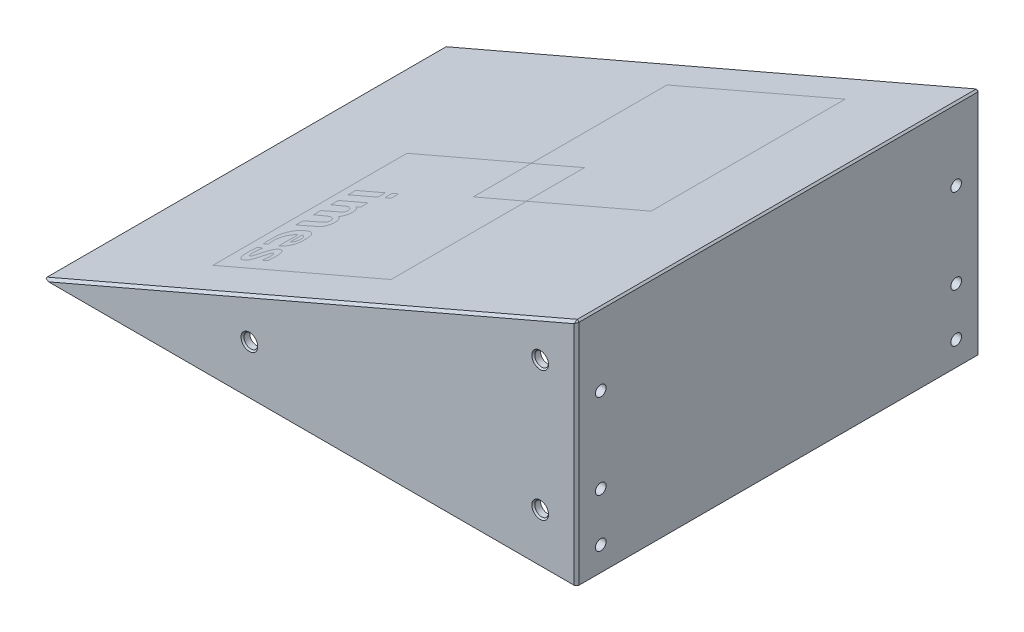
SolidWorks part; units mm, degrees
note: The reader was unsure of these and kept them because the rebuilt part matched: shared geometry of "Sketch13<3>", "Sketch13<4>".
ref_plane "Front Plane" through (0, 0, 0) normal (0, 0, 1) x (1, 0, 0)
ref_plane "Top Plane" through (0, 0, 0) normal (0, 1, 0) x (1, 0, 0)
ref_plane "Right Plane" through (0, 0, 0) normal (1, 0, 0) x (0, 0, -1)
sketch "Sketch1" plane through (0, 0, 0) normal (0, 0, 1) x (1, 0, 0)
  line L0 (0, 0) -> (-220.3974, 0)
  line L1 (-220.3974, 0) -> (0, 95)
  line L2 (0, 95) -> (0, 0)
  dimension "D1" = 240
extrude "Boss-Extrude1" add sketch "Sketch1" along normal blind 166.6667
ref_plane "Plane1" through (0, 0, 163.6667) normal (0, 0, 1) x (1, 0, 0)
sketch "Sketch2" plane through (0, 0, 163.6667) normal (0, 0, 1) x (1, 0, 0)
  line L0 (-5, 0) -> (-5, 87.4001)
  line L1 (-220.3974, 0) -> (0, 0) construction
  line L2 (-5, 87.4001) -> (-178.2213, 12.7348)
  line L3 (-178.2213, 12.7348) -> (-178.2213, 0)
  line L4 (-178.2213, 0) -> (-5, 0)
  line L5 (0, 95) -> (-220.3974, 0) construction
  line L6 (0, 0) -> (0, 95) construction
  dimension "D1" = 188.628
  dimension "D2" = 5
  dimension "D3" = 5
extrude "Cut-Extrude1" cut sketch "Sketch2" against normal offset from surface (160.6667 mm away) 3 up to face at (-73.4658, 31.6667, 0)
sketch "Sketch3" plane through (0, 0, 0) normal (1, 0, 0) x (0, 0, -1)
  line L0 (-156.6667, 0) -> (-156.6667, 95) construction
  line L1 (-166.6667, 0) -> (0, 0) construction
  line L2 (-166.6667, 95) -> (0, 95) construction
  line L3 (-166.6667, 0) -> (-166.6667, 95) construction
  line L4 (-83.3333, 95) -> (-83.3333, 0) construction
  line L5 (-10, 0) -> (-10, 95) construction
  circle A0 centre (-156.6667, 10) radius 2.2
  circle A1 centre (-156.6667, 65) radius 2.2
  circle A2 centre (-156.6667, 30) radius 2.2
  circle A3 centre (-10, 30) radius 2.2
  circle A4 centre (-10, 65) radius 2.2
  circle A5 centre (-10, 10) radius 2.2
  dimension "D2" = 4.4
  dimension "D3" = 10
  dimension "D4" = 20
  dimension "D5" = 30
  dimension "D1" = 10
extrude "Cut-Extrude2" cut sketch "Sketch3" against normal up to surface (5 mm away) up to face at (-5, 43.7, 83.3333)
sketch "Sketch4" plane through (0, 0, 0) normal (0, 0, -1) x (-1, 0, 0)
  line L0 (15, 0) -> (15, 88.5344) construction
  line L1 (220.3974, 0) -> (0, 0) construction
  line L2 (0, 95) -> (220.3974, 0) construction
  line L3 (0, 0) -> (0, 95) construction
  line L4 (15, 20) -> (135, 20) construction
  circle A0 centre (15, 73.5344) radius 2.2
  circle A1 centre (15, 20) radius 2.2
  circle A2 centre (135, 20) radius 2.2
  dimension "D1" = 4.4
  dimension "D2" = 20
  dimension "D3" = 15
  dimension "D4" = 15
  dimension "D5" = 120
extrude "Cut-Extrude3" cut sketch "Sketch4" against normal up to surface (163.6667 mm away)
ref_plane "Plane2" through (0, 0, 83.3333) normal (0, 0, -1) x (-1, 0, 0)
mirror "Mirror1" about plane through (0, 0, 83.3333) normal (0, 0, -1) of "Cut-Extrude3"
chamfer "Chamfer1" distance 1 angle 45 6 edges at (-220.3974, 0, 83.3333) (0, 95, 83.3333) (0, 47.5, 166.6667) (-110.1987, 47.5, 166.6667) (0, 47.5, 0) (-110.1987, 47.5, 0)
sketch "Sketch13" plane through (-166.8801, 23.068, 13.9635) normal (-0.3958, 0.9183, 0) x (0, 0, 1)
  line L0 (55.9477, 28.1093) -> (55.9477, 56.0832)
  line L1 (55.9477, 56.0832) -> (27.9739, 56.0832)
  line L2 (27.9739, 56.0832) -> (0, 56.0832)
  line L3 (0, 56.0832) -> (0, 96.1136)
  line L4 (0, 96.1136) -> (0, 136.144)
  line L5 (0, 136.144) -> (40.0304, 136.144)
  line L6 (40.0304, 136.144) -> (80.0608, 136.144)
  line L7 (80.0608, 136.144) -> (80.0608, 108.1701)
  line L8 (80.0608, 108.1701) -> (80.0608, 80.1962)
  line L9 (80.0608, 80.1962) -> (108.0347, 80.1962)
  line L10 (108.0347, 80.1962) -> (136.0085, 80.1962)
  line L11 (136.0085, 80.1962) -> (136.0085, 40.1658)
  line L12 (136.0085, 40.1658) -> (136.0085, 0.1354)
  line L13 (136.0085, 0.1354) -> (95.9781, 0.1354)
  line L14 (95.9781, 0.1354) -> (55.9477, 0.1354)
  line L15 (55.9477, 0.1354) -> (55.9477, 28.1093)
  line L16 (119.38, 5.285) -> (120.0235, 5.4406)
  line L17 (120.0235, 5.4406) -> (120.0235, 6.5278)
  line L18 (116.4971, 12.8693) -> (120.4299, 12.8693)
  line L19 (120.4299, 12.8693) -> (120.4288, 13.445)
  line L20 (119.3798, 5.285) -> (119.38, 5.285)
  line L21 (117.4134, 15.1659) -> (117.4853, 14.6304)
  line L22 (117.4853, 14.6304) -> (115.029, 14.6304)
  line L23 (130.3189, 17.2595) -> (130.3189, 18.5339)
  line L24 (130.3189, 18.5339) -> (129.0181, 18.7681)
  line L25 (84.9376, 11.9888) -> (84.9376, 18.6944)
  line L26 (84.9376, 18.6944) -> (83.3797, 18.6944)
  line L27 (83.3797, 18.6944) -> (81.8219, 18.6944)
  line L28 (81.8219, 18.6944) -> (81.8219, 11.9888)
  line L29 (81.8219, 11.9888) -> (81.8219, 5.2832)
  line L30 (81.8219, 5.2832) -> (83.3797, 5.2832)
  line L31 (83.3797, 5.2832) -> (84.9376, 5.2832)
  line L32 (84.9376, 5.2832) -> (84.9376, 11.9888)
  line L33 (95.7918, 15.6286) -> (96.1136, 15.2862)
  line L34 (96.1136, 15.2862) -> (96.1522, 10.2847)
  line L35 (96.1522, 10.2847) -> (96.1909, 5.2832)
  line L36 (96.1909, 5.2832) -> (97.744, 5.2832)
  line L37 (97.744, 5.2832) -> (99.2971, 5.2832)
  line L38 (99.2971, 5.2832) -> (99.2996, 8.5682)
  line L39 (103.4721, 10.1261) -> (103.5151, 5.2832)
  line L40 (103.5151, 5.2832) -> (105.0018, 5.2832)
  line L41 (105.0018, 5.2832) -> (106.4885, 5.2832)
  line L42 (106.4885, 5.2832) -> (106.4489, 10.7357)
  line L43 (99.574, 17.0612) -> (99.077, 16.2924)
  line L44 (99.077, 16.2924) -> (98.8423, 16.9531)
  line L45 (92.5097, 17.2277) -> (92.1175, 16.6093)
  line L46 (92.1175, 16.6093) -> (92.1175, 17.6519)
  line L47 (92.1175, 17.6519) -> (92.1175, 18.6944)
  line L48 (92.1175, 18.6944) -> (90.5597, 18.6944)
  line L49 (90.5597, 18.6944) -> (89.0018, 18.6944)
  line L50 (89.0018, 18.6944) -> (89.0018, 11.9888)
  line L51 (89.0018, 11.9888) -> (89.0018, 5.2832)
  line L52 (89.0018, 5.2832) -> (90.5503, 5.2832)
  line L53 (90.5503, 5.2832) -> (92.0987, 5.2832)
  line L54 (92.0987, 5.2832) -> (92.1453, 9.1101)
  line L55 (84.9376, 23.1648) -> (84.9376, 24.6549)
  line L56 (84.9376, 24.6549) -> (83.3797, 24.6549)
  line L57 (83.3797, 24.6549) -> (81.8219, 24.6549)
  line L58 (81.8219, 24.6549) -> (81.8219, 23.1648)
  line L59 (81.8219, 23.1648) -> (81.8219, 21.6746)
  line L60 (81.8219, 21.6746) -> (83.3797, 21.6746)
  line L61 (83.3797, 21.6746) -> (84.9376, 21.6746)
  line L62 (84.9376, 21.6746) -> (84.9376, 23.1648)
  line L63 (80.0277, 68.1058) -> (80.0623, 80.0608)
  line L64 (80.0623, 80.0608) -> (68.0727, 80.0608)
  line L65 (68.0727, 80.0608) -> (56.0832, 80.0608)
  line L66 (56.0832, 80.0608) -> (56.0832, 68.0712)
  line L67 (56.0832, 68.0712) -> (56.0832, 56.0817)
  line L68 (56.0832, 56.0817) -> (68.0381, 56.1163)
  line L69 (68.0381, 56.1163) -> (79.9931, 56.1509)
  line L70 (79.9931, 56.1509) -> (80.0277, 68.1058)
  line L71 (56.0832, 56.0817) -> (55.9477, 56.0832)
  line L72 (80.0623, 80.0608) -> (80.0608, 80.2508)
  spline S0 degree 3 poles (120.0235, 6.5278) (120.0235, 7.4768) (119.9954, 7.6043) (119.8028, 7.5304) knots 0 0 0 0 1 1 1 1
  spline S1 degree 3 poles (119.8028, 7.5304) (119.096, 7.2592) (118.2565, 7.1534) (117.2109, 7.2036) knots 0 0 0 0 1 1 1 1
  spline S2 degree 3 poles (117.2109, 7.2036) (116.2244, 7.2511) (115.9063, 7.3264) (115.3017, 7.6558) knots 0 0 0 0 1 1 1 1
  spline S3 degree 3 poles (115.3017, 7.6558) (113.9807, 8.3756) (112.9036, 9.9548) (112.5572, 11.6798) knots 0 0 0 0 1 1 1 1
  spline S4 degree 3 poles (112.5572, 11.6798) (112.3015, 12.9531) (112.024, 12.8693) (116.4971, 12.8693) knots 0 0 0 0 1 1 1 1
  spline S5 degree 3 poles (120.4288, 13.445) (120.4268, 15.0769) (119.8192, 16.8204) (118.9624, 17.6545) knots 0 0 0 0 1 1 1 1
  spline S6 degree 3 poles (118.9624, 17.6545) (118.689, 17.9206) (118.0996, 18.3072) (117.6526, 18.5136) knots 0 0 0 0 1 1 1 1
  spline S7 degree 3 poles (117.6526, 18.5136) (116.9232, 18.8503) (116.6868, 18.8893) (115.3496, 18.8932) knots 0 0 0 0 1 1 1 1
  spline S8 degree 3 poles (115.3496, 18.8932) (113.601, 18.8983) (112.619, 18.6494) (111.7388, 17.9781) knots 0 0 0 0 1 1 1 1
  spline S9 degree 3 poles (111.7388, 17.9781) (110.8801, 17.3232) (110.3098, 16.4939) (109.966, 15.4003) knots 0 0 0 0 1 1 1 1
  spline S10 degree 3 poles (109.966, 15.4003) (109.5683, 14.1354) (109.537, 11.2699) (109.9059, 9.889) knots 0 0 0 0 1 1 1 1
  spline S11 degree 3 poles (109.9059, 9.889) (110.5643, 7.4241) (112.0357, 5.8283) (114.2123, 5.2184) knots 0 0 0 0 1 1 1 1
  spline S12 degree 3 poles (114.2123, 5.2184) (115.0598, 4.9809) (118.2945, 5.0226) (119.3798, 5.285) knots 0 0 0 0 1 1 1 1
  spline S13 degree 3 poles (112.5728, 14.8379) (112.5728, 15.2621) (112.9536, 15.9345) (113.4314, 16.354) knots 0 0 0 0 1 1 1 1
  spline S14 degree 3 poles (113.4314, 16.354) (114.8968, 17.6406) (117.1726, 16.9616) (117.4134, 15.1659) knots 0 0 0 0 1 1 1 1
  spline S15 degree 3 poles (115.029, 14.6304) (112.9131, 14.6304) (112.5728, 14.6591) (112.5728, 14.8379) knots 0 0 0 0 1 1 1 1
  spline S16 degree 3 poles (128.0837, 5.1959) (130.1184, 5.7381) (131.1308, 6.9611) (131.1274, 8.873) knots 0 0 0 0 1 1 1 1
  spline S17 degree 3 poles (131.1274, 8.873) (131.1244, 10.659) (130.5305, 11.4345) (127.802, 13.2159) knots 0 0 0 0 1 1 1 1
  spline S18 degree 3 poles (127.802, 13.2159) (125.8156, 14.5128) (125.3067, 14.9859) (125.3067, 15.5356) knots 0 0 0 0 1 1 1 1
  spline S19 degree 3 poles (125.3067, 15.5356) (125.3067, 16.2783) (126.7192, 16.9245) (127.9105, 16.7268) knots 0 0 0 0 1 1 1 1
  spline S20 degree 3 poles (127.9105, 16.7268) (128.2293, 16.6739) (128.8784, 16.4854) (129.3529, 16.3078) knots 0 0 0 0 1 1 1 1
  spline S21 degree 3 poles (129.3529, 16.3078) (129.8275, 16.1303) (130.2389, 15.985) (130.2673, 15.985) knots 0 0 0 0 1 1 1 1
  spline S22 degree 3 poles (130.2673, 15.985) (130.2957, 15.985) (130.3189, 16.5585) (130.3189, 17.2595) knots 0 0 0 0 1 1 1 1
  spline S23 degree 3 poles (129.0181, 18.7681) (125.2165, 19.4526) (122.5963, 17.9842) (122.6016, 15.1722) knots 0 0 0 0 1 1 1 1
  spline S24 degree 3 poles (122.6016, 15.1722) (122.6047, 13.5145) (123.3273, 12.5517) (125.8526, 10.8401) knots 0 0 0 0 1 1 1 1
  spline S25 degree 3 poles (125.8526, 10.8401) (127.7723, 9.539) (128.2869, 9.0543) (128.2869, 8.5476) knots 0 0 0 0 1 1 1 1
  spline S26 degree 3 poles (128.2869, 8.5476) (128.2869, 7.2086) (125.4698, 6.9556) (122.8344, 8.0578) knots 0 0 0 0 1 1 1 1
  spline S27 degree 3 poles (122.8344, 8.0578) (122.6177, 8.1484) (122.5973, 8.0392) (122.5973, 6.7878) knots 0 0 0 0 1 1 1 1
  spline S28 degree 3 poles (122.5973, 6.7878) (122.5973, 5.7874) (122.6429, 5.4163) (122.7667, 5.4099) knots 0 0 0 0 1 1 1 1
  spline S29 degree 3 poles (122.7667, 5.4099) (122.8598, 5.4053) (123.3017, 5.3188) (123.7488, 5.2181) knots 0 0 0 0 1 1 1 1
  spline S30 degree 3 poles (123.7488, 5.2181) (124.8105, 4.9789) (127.2228, 4.9665) (128.0837, 5.1959) knots 0 0 0 0 1 1 1 1
  spline S31 degree 3 poles (92.1453, 9.1101) (92.1899, 12.7599) (92.207, 12.9747) (92.5133, 13.7498) knots 0 0 0 0 1 1 1 1
  spline S32 degree 3 poles (92.5133, 13.7498) (92.999, 14.9787) (93.5089, 15.6452) (94.1635, 15.9072) knots 0 0 0 0 1 1 1 1
  spline S33 degree 3 poles (94.1635, 15.9072) (94.8473, 16.1808) (95.3543, 16.0941) (95.7918, 15.6286) knots 0 0 0 0 1 1 1 1
  spline S34 degree 3 poles (99.2996, 8.5682) (99.3022, 12.0563) (99.4174, 13.0342) (99.9806, 14.3433) knots 0 0 0 0 1 1 1 1
  spline S35 degree 3 poles (99.9806, 14.3433) (100.5254, 15.6097) (101.6839, 16.3432) (102.5638, 15.9787) knots 0 0 0 0 1 1 1 1
  spline S36 degree 3 poles (102.5638, 15.9787) (103.3998, 15.6324) (103.4245, 15.4734) (103.4721, 10.1261) knots 0 0 0 0 1 1 1 1
  spline S37 degree 3 poles (106.4489, 10.7357) (106.4099, 16.0999) (106.4042, 16.1992) (106.0972, 16.8656) knots 0 0 0 0 1 1 1 1
  spline S38 degree 3 poles (106.0972, 16.8656) (105.5361, 18.0835) (104.6197, 18.7738) (103.367, 18.9222) knots 0 0 0 0 1 1 1 1
  spline S39 degree 3 poles (103.367, 18.9222) (101.906, 19.0952) (100.4161, 18.3642) (99.574, 17.0612) knots 0 0 0 0 1 1 1 1
  spline S40 degree 3 poles (98.8423, 16.9531) (98.5273, 17.84) (97.8459, 18.4967) (96.9708, 18.7566) knots 0 0 0 0 1 1 1 1
  spline S41 degree 3 poles (96.9708, 18.7566) (95.1569, 19.2952) (93.4499, 18.7102) (92.5097, 17.2277) knots 0 0 0 0 1 1 1 1
extrude "Cut-Extrude7" cut sketch "Sketch13" against normal blind 1 contours L15 L14 L13 L12 L11 L10 L9 L8 L7 L6 L5 L4 L3 L2 L1 L0 S41 S40 L44 L43 S39 S38 S37 L42 L41 L40 L39 S36 S35 S34 L38 L37 L36 L35 L34 L33 S33 S32 S31 L54 L53 L52 L51 L50 L49 L48 L47 L46 L45 | S15 L22 L21 S14 S13 | L64 L72 L9 L8 L7 L6 L5 L4 L3 L2 L1 L71 L67 L66 L65
extrude "Boss-Extrude5" add sketch "Sketch13<3>" against normal up to surface (1 mm away) separate body contours S15 L22 L21 S14 S13 | L15 L14 L13 L12 L11 L10 L9 L8 L7 L6 L5 L4 L3 L2 L1 L0 S41 S40 L44 L43 S39 S38 S37 L42 L41 L40 L39 S36 S35 S34 L38 L37 L36 L35 L34 L33 S33 S32 S31 L54 L53 L52 L51 L50 L49 L48 L47 L46 L45
sketch "Sketch13<3>" plane through (-166.8801, 23.068, 13.9635) normal (-0.3958, 0.9183, 0) x (0, 0, 1) same geometry as "Sketch13"
extrude "Boss-Extrude6" add sketch "Sketch13<4>" against normal up to surface (1 mm away) separate body contours L64 L72 L9 L8 L7 L6 L5 L4 L3 L2 L1 L71 L67 L66 L65 up to face at (-103.9101, 49.1217, 81.9678)
sketch "Sketch13<4>" plane through (-166.8801, 23.068, 13.9635) normal (-0.3958, 0.9183, 0) x (0, 0, 1) same geometry as "Sketch13"
sketch "Sketch14" plane through (0, 0, 166.6667) normal (0, 0, 1) x (1, 0, 0)
  circle A0 centre (-135, 20) radius 2.85
  circle A1 centre (-15, 20) radius 2.85
  circle A2 centre (-15, 73.5344) radius 2.85
  point P9 (0, 0)
  dimension "D1" = 5.7
extrude "Einschmelzgewinde" cut sketch "Sketch14" against normal through all
chamfer "Chamfer2" distance 0.6 angle 45 6 edges at (-132.15, 20, 0) (-12.15, 20, 0) (-12.15, 73.5344, 0) (-12.15, 20, 166.6667) (-12.15, 73.5344, 166.6667) (-132.15, 20, 166.6667)
